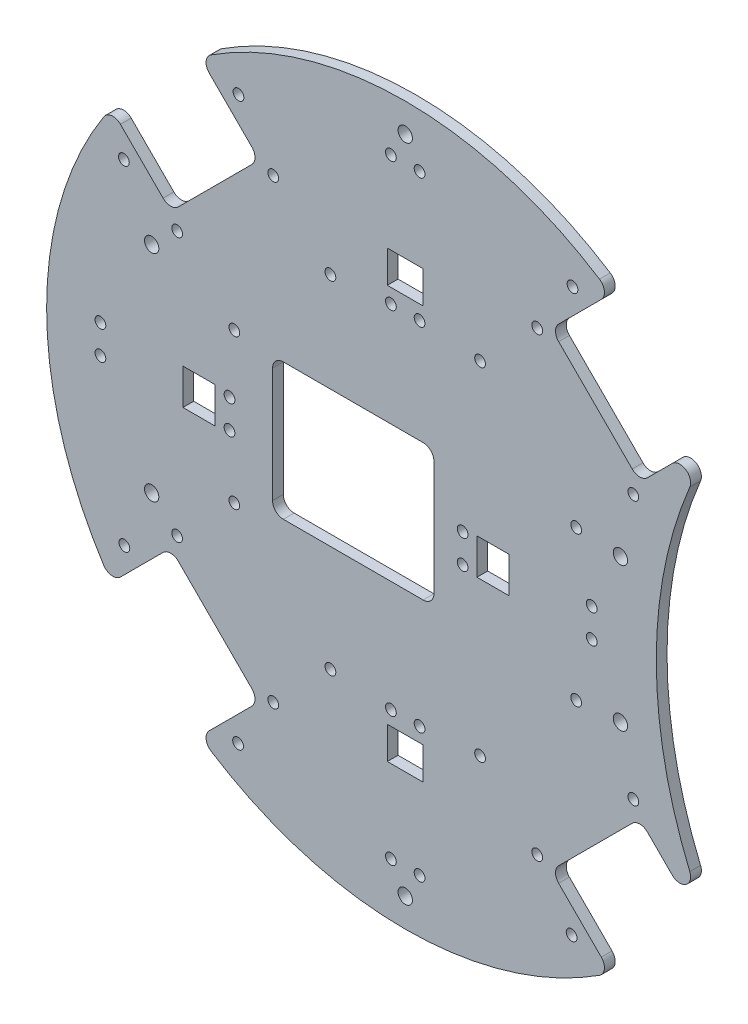
SolidWorks part; units mm, degrees
material "Caoba"
ref_plane "Alzado" through (0, 0, 0) normal (0, 0, 1) x (1, 0, 0)
ref_plane "Planta" through (0, 0, 0) normal (0, 1, 0) x (1, 0, 0)
ref_plane "Vista lateral" through (0, 0, 0) normal (1, 0, 0) x (0, 0, -1)
sketch "Croquis1" plane through (0, 0, 0) normal (0, 0, 1) x (1, 0, 0)
  circle A0 centre (0, 0) radius 100
  dimension "D1" = 200
extrude "Saliente-Extruir1" add sketch "Croquis1" along normal blind 3
sketch "Croquis3" plane through (0, 0, 3) normal (0, 0, 1) x (1, 0, 0)
  line L0 (0, 0) -> (190, 0) construction
  circle A0 centre (190, 0) radius 120
  dimension "D1" = 240
  dimension "D2" = 190
extrude "Cortar-Extruir1" cut sketch "Croquis3" against normal blind 3
sketch "Croquis5" plane through (0, 0, 3) normal (0, 0, 1) x (1, 0, 0)
  line L0 (0, -100) -> (0, 100) construction
  line L1 (-100, 0) -> (70, 0) construction
  line L2 (0, 0) -> (-70.7107, -70.7107) construction
  line L3 (-70.7107, -70.7107) -> (70.7107, 70.7107) construction
  line L4 (0, 0) -> (-70.7107, 70.7107) construction
  line L5 (-70.7107, 70.7107) -> (70.7107, -70.7107) construction
  line L6 (-70.7107, -70.7107) -> (-58.3363, -83.085) construction
  line L9 (-58.3363, -83.085) -> (-83.085, -58.3363)
  line L11 (-83.085, -58.3363) -> (-65.4074, -40.6586)
  line L12 (-65.4074, -40.6586) -> (-40.6586, -65.4074)
  line L13 (-40.6586, -65.4074) -> (-58.3363, -83.085)
  line L14 (-70.7107, 70.7107) -> (-83.085, 58.3363) construction
  line L15 (-83.085, 58.3363) -> (-100, 0) construction
  line L17 (-83.085, 58.3363) -> (-58.3363, 83.085)
  line L18 (-58.3363, 83.085) -> (-40.6586, 65.4074)
  line L19 (-40.6586, 65.4074) -> (-65.4074, 40.6586)
  line L20 (-65.4074, 40.6586) -> (-83.085, 58.3363)
  line L22 (70.7107, -70.7107) -> (58.3363, -83.085) construction
  line L23 (58.3363, -83.085) -> (0, -100) construction
  line L24 (58.3363, -83.085) -> (83.085, -58.3363)
  line L25 (83.085, -58.3363) -> (65.4074, -40.6586)
  line L26 (65.4074, -40.6586) -> (40.6586, -65.4074)
  line L27 (40.6586, -65.4074) -> (58.3363, -83.085)
  line L28 (70.7107, 70.7107) -> (58.3363, 83.085) construction
  line L29 (58.3363, 83.085) -> (0, 100) construction
  line L30 (58.3363, 83.085) -> (83.085, 58.3363)
  line L31 (83.085, 58.3363) -> (65.4074, 40.6586)
  line L32 (65.4074, 40.6586) -> (40.6586, 65.4074)
  line L33 (40.6586, 65.4074) -> (58.3363, 83.085)
  arc A0 (83.4211, 55.1446) -> (83.4211, -55.1446) centre (0, 0) ccw construction
  arc A1 (83.4211, 55.1446) -> (83.4211, -55.1446) centre (190, 0) ccw construction
  point P36 (0, 0)
  dimension "D2" = 17.5
  dimension "D3" = 25
  dimension "D4" = 35
  dimension "D5" = 25
  dimension "D6" = 35
  dimension "D8" = 25
  dimension "D9" = 17.5
  dimension "D7" = 35
  dimension "D10" = 90
  dimension "D11" = 17.5
  dimension "D12" = 17.5
  dimension "D13" = 35
  dimension "D14" = 25
  dimension "D15" = 134.3503
  dimension "D16" = 100
extrude "Cortar-Extruir6" cut sketch "Croquis5" against normal blind 10
sketch "Croquis12" plane through (0, 0, 3) normal (0, 0, 1) x (1, 0, 0)
  line L0 (-53.033, -53.033) -> (-39.9421, -50.0116) construction
  line L1 (-40.6586, -65.4074) -> (-65.4074, -40.6586) construction
  line L2 (-39.9421, -50.0116) -> (-36.8049, -63.6043) construction
  line L3 (-36.8049, -63.6043) -> (-63.6043, -36.8049) construction
  line L4 (-63.6043, -36.8049) -> (-47.6661, -20.8667) construction
  line L6 (53.033, -53.033) -> (-53.033, 53.033) construction
  line L7 (65.4074, -40.6586) -> (40.6586, -65.4074) construction
  line L8 (-65.4074, 40.6586) -> (-40.6586, 65.4074) construction
  line L9 (36.8049, 63.6043) -> (20.8667, 47.6661) construction
  line L10 (63.6043, 36.8049) -> (36.8049, 63.6043) construction
  line L11 (50.0116, 39.9421) -> (63.6043, 36.8049) construction
  line L12 (53.033, 53.033) -> (50.0116, 39.9421) construction
  line L14 (53.033, -53.033) -> (50.2046, -50.2046) construction
  line L15 (50.2046, -50.2046) -> (36.8049, -63.6043) construction
  line L16 (36.8049, -63.6043) -> (63.6043, -36.8049) construction
  line L17 (63.6043, -36.8049) -> (47.6661, -20.8667) construction
  line L19 (-53.033, -53.033) -> (53.033, 53.033) construction
  line L20 (-36.8049, 63.6043) -> (-20.8667, 47.6661) construction
  line L21 (-63.6043, 36.8049) -> (-36.8049, 63.6043) construction
  line L22 (-50.2046, 50.2046) -> (-63.6043, 36.8049) construction
  line L23 (-53.033, 53.033) -> (-50.2046, 50.2046) construction
  circle A0 centre (-63.6043, -36.8049) radius 1.5
  circle A1 centre (-36.8049, -63.6043) radius 1.5
  circle A2 centre (-47.6661, -20.8667) radius 1.5
  circle A3 centre (-20.8667, -47.6661) radius 1.5
  circle A5 centre (47.6661, 20.8667) radius 1.5
  circle A6 centre (20.8667, 47.6661) radius 1.5
  circle A7 centre (63.6043, 36.8049) radius 1.5
  circle A8 centre (36.8049, 63.6043) radius 1.5
  circle A10 centre (20.8667, -47.6661) radius 1.5
  circle A11 centre (47.6661, -20.8667) radius 1.5
  circle A12 centre (63.6043, -36.8049) radius 1.5
  circle A13 centre (36.8049, -63.6043) radius 1.5
  circle A15 centre (-63.6043, 36.8049) radius 1.5
  circle A16 centre (-36.8049, 63.6043) radius 1.5
  circle A17 centre (-20.8667, 47.6661) radius 1.5
  circle A18 centre (-47.6661, 20.8667) radius 1.5
  dimension "D2" = 3
  dimension "D3" = 3
  dimension "D4" = 4
  dimension "D5" = 4
  dimension "D6" = 3
  dimension "D7" = 3
  dimension "D8" = 37.9
  dimension "D9" = 22.54
  dimension "D10" = 22.54
  dimension "D11" = 37.9
  dimension "D12" = 18.95
  dimension "D13" = 18.95
  dimension "D14" = 3
  dimension "D15" = 3
  dimension "D16" = 3
  dimension "D17" = 3
  dimension "D18" = 37.9
  dimension "D19" = 22.54
  dimension "D20" = 22.54
  dimension "D21" = 37.9
  dimension "D22" = 4
  dimension "D1" = 13.95
extrude "Cortar-Extruir7" cut sketch "Croquis12" against normal through all
sketch "Croquis9" plane through (0, 0, 3) normal (0, 0, 1) x (1, 0, 0)
  line L0 (0, 0) -> (-100, 0) construction
  line L5 (0, 100) -> (0, -100) construction
  line L6 (20, 5) -> (29, 5)
  line L7 (20, 5) -> (20, -5)
  line L8 (20, -5) -> (29, -5)
  line L9 (29, 5) -> (29, -5)
  line L10 (-5, -53) -> (5, -53)
  line L11 (-53, 5) -> (-62, 5)
  line L12 (-53, 5) -> (-53, -5)
  line L13 (-53, -5) -> (-62, -5)
  line L14 (-62, 5) -> (-62, -5)
  line L15 (-5, 62) -> (5, 62)
  line L16 (-5, 62) -> (-5, 53)
  line L17 (-5, 53) -> (5, 53)
  line L18 (5, 62) -> (5, 53)
  line L19 (5, -62) -> (5, -53)
  line L20 (-5, -62) -> (5, -62)
  line L21 (-5, -62) -> (-5, -53)
  line L22 (0, 0) -> (70, 0) construction
  line L24 (-52.061, -4) -> (-52.0837, -4) construction
  circle A0 centre (52, -4) radius 1.5
  circle A1 centre (16, 4) radius 1.5
  circle A2 centre (20.8667, 47.6661) radius 1.5 construction
  circle A4 centre (52, 4) radius 1.5
  circle A5 centre (16, -4) radius 1.5
  arc A6 (-81.9939, 57.2451) -> (-81.9939, -57.2451) centre (0, 0) ccw construction
  arc A7 (83.4211, 55.1446) -> (83.4211, -55.1446) centre (190, 0) ccw construction
  circle A8 centre (-85, 4) radius 1.5
  circle A9 centre (-85, -4) radius 1.5
  circle A10 centre (-49, 4) radius 1.5
  circle A11 centre (-49, -4) radius 1.5
  circle A12 centre (-4, 85) radius 1.5
  circle A13 centre (4, 85) radius 1.5
  circle A14 centre (-4, 49) radius 1.5
  circle A15 centre (4, 49) radius 1.5
  circle A20 centre (-4, -49) radius 1.5
  circle A21 centre (4, -49) radius 1.5
  circle A22 centre (4, -85) radius 1.5
  circle A23 centre (-4, -85) radius 1.5
  arc A25 (57.2451, 81.9939) -> (-57.2451, 81.9939) centre (0, 0) ccw construction
  point P2 (0, 0)
  dimension "D6" = 16
  dimension "D7" = 3
  dimension "D8" = 36
  dimension "D9" = 36
  dimension "D10" = 3
  dimension "D11" = 3
  dimension "D12" = 4
  dimension "D13" = 4
  dimension "D14" = 3
  dimension "D15" = 3
  dimension "D16" = 3
  dimension "D21" = 4
  dimension "D22" = 4
  dimension "D23" = 3
  dimension "D24" = 3
  dimension "D25" = 4
  dimension "D26" = 4
  dimension "D27" = 36
  dimension "D28" = 5
  dimension "D29" = 85
  dimension "D30" = 85
  dimension "D35" = 3
  dimension "D36" = 3
  dimension "D37" = 5
  dimension "D38" = 4
  dimension "D39" = 3
  dimension "D40" = 3
  dimension "D41" = 8
  dimension "D42" = 36
  dimension "D43" = 36
  dimension "D44" = 36
  dimension "D45" = 4
  dimension "D46" = 4
  dimension "D51" = 4
  dimension "D52" = 4
  dimension "D53" = 16
  dimension "D55" = 36
  dimension "D56" = 49
  dimension "D57" = 49
  dimension "D58" = 3
  dimension "D59" = 3
  dimension "D60" = 3
  dimension "D61" = 3
  dimension "D62" = 9
  dimension "D32" = 10
  dimension "D64" = 4
  dimension "D71" = 85.0941
  dimension "D72" = 85.0941
  dimension "D19" = 4
  dimension "D31" = 36
  dimension "D49" = 4
  dimension "D50" = 5
  dimension "D65" = 4
  dimension "D68" = 16.9194
  dimension "D17" = 9
  dimension "D18" = 10
  dimension "D20" = 4
  dimension "D33" = 5
  dimension "D34" = 4
  dimension "D47" = 10
  dimension "D48" = 9
  dimension "D54" = 4
  dimension "D63" = 4
  dimension "D66" = 9
  dimension "D67" = 10
extrude "Cortar-Extruir5" cut sketch "Croquis9" against normal blind 10
sketch "Croquis13" plane through (0, 0, 3) normal (0, 0, 1) x (1, 0, 0)
  line L0 (0, 100) -> (0, -100) construction
  line L1 (-100, 0) -> (70, 0) construction
  line L2 (-70.7107, 70.7107) -> (70.7107, -70.7107) construction
  line L3 (-70.7093, -70.7093) -> (70.712, 70.712) construction
  line L4 (-70.7107, 70.7107) -> (-70.7093, -70.7093) construction
  line L5 (-70.7093, -70.7093) -> (70.7107, -70.7107) construction
  line L6 (70.7107, -70.7107) -> (70.712, 70.712) construction
  line L7 (70.712, 70.712) -> (-70.7107, 70.7107) construction
  line L9 (-37, 20) -> (8, 20)
  line L10 (-37, 20) -> (-37, -18)
  line L11 (-37, -18) -> (8, -18)
  line L12 (8, 20) -> (8, -18)
  arc A0 (57.2451, 81.9939) -> (-57.2451, 81.9939) centre (0, 0) ccw construction
  arc A1 (-57.2451, -81.9939) -> (57.2451, -81.9939) centre (0, 0) ccw construction
  arc A2 (-81.9939, 57.2451) -> (-81.9939, -57.2451) centre (0, 0) ccw construction
  arc A3 (83.4211, 55.1446) -> (83.4211, -55.1446) centre (190, 0) ccw construction
  circle A4 centre (-70.7103, 30) radius 2
  circle A5 centre (-70.7097, -30) radius 2
  circle A8 centre (0, -92) radius 2
  circle A9 centre (0, 92) radius 2
  circle A10 centre (60, -20) radius 2
  circle A11 centre (60, 20) radius 2
  point P37 (-15, 0)
  dimension "D9" = 4
  dimension "D10" = 4
  dimension "D11" = 30
  dimension "D12" = 30
  dimension "D13" = 4
  dimension "D14" = 4
  dimension "D15" = 60
  dimension "D16" = 60
  dimension "D17" = 4
  dimension "D18" = 92
  dimension "D19" = 92
  dimension "D20" = 4
  dimension "D25" = 20
  dimension "D26" = 20
  dimension "D1" = 45
  dimension "D2" = 200
  dimension "D3" = 0
  dimension "D4" = 200
  dimension "D5" = 45
  dimension "D6" = 0
  dimension "D7" = 141.42
  dimension "D8" = 141.42
  dimension "D21" = 45
  dimension "D22" = 38
  dimension "D23" = 18
  dimension "D24" = 37
extrude "Cortar-Extruir8" cut sketch "Croquis13" against normal through all
fillet "Redondeo2" radius 3 20 edges at (-81.9939, 57.2451, 1.5) (-65.4074, 40.6586, 1.5) (-40.6586, 65.4074, 1.5) (-57.2451, 81.9939, 1.5) (65.4074, 40.6586, 1.5) (40.6586, 65.4074, 1.5) (57.2451, 81.9939, 1.5) (81.9939, 57.2451, 1.5) (65.4074, -40.6586, 1.5) (40.6586, -65.4074, 1.5) (81.9939, -57.2451, 1.5) (57.2451, -81.9939, 1.5) (-65.4074, -40.6586, 1.5) (-81.9939, -57.2451, 1.5) (-57.2451, -81.9939, 1.5) (-40.6586, -65.4074, 1.5) (8, -18, 1.5) (8, 20, 1.5) (-37, -18, 1.5) (-37, 20, 1.5)
fillet "Redondeo3" radius 3 2 edges at (83.4211, -55.1446, 1.5) (83.4211, 55.1446, 1.5)
sketch "Croquis14" plane through (0, 0, 3) normal (0, 0, 1) x (1, 0, 0)
  line L0 (42.78, -67.5287) -> (54.6657, -79.4145) construction
  line L1 (-54.6657, -79.4145) -> (-42.78, -67.5287) construction
  line L3 (-67.5287, -42.78) -> (-79.4145, -54.6657) construction
  line L4 (-79.4145, 54.6657) -> (-67.5287, 42.78) construction
  line L5 (-42.78, 67.5287) -> (-54.6657, 79.4145) construction
  line L6 (54.6657, 79.4145) -> (42.78, 67.5287) construction
  circle A0 centre (46.3901, -78.2099) radius 1.5
  circle A1 centre (36.8049, -63.6043) radius 1.5 construction
  circle A2 centre (-46.6139, -78.4337) radius 1.5
  circle A3 centre (-36.8049, -63.6043) radius 1.5 construction
  circle A4 centre (-78.3182, -46.4984) radius 1.5
  circle A5 centre (-78.4553, 46.6355) radius 1.5
  circle A6 centre (-46.4984, 78.3182) radius 1.5
  circle A7 centre (46.6355, 78.4553) radius 1.5
  circle A8 centre (-63.6043, -36.8049) radius 1.5 construction
  circle A9 centre (-63.6043, 36.8049) radius 1.5 construction
  circle A10 centre (36.8049, 63.6043) radius 1.5 construction
  circle A11 centre (-36.8049, 63.6043) radius 1.5 construction
  dimension "D1" = 3
  dimension "D2" = 5
  dimension "D3" = 17.47
  dimension "D4" = 3
  dimension "D5" = 17.78
  dimension "D7" = 3
  dimension "D8" = 3
  dimension "D9" = 3
  dimension "D10" = 3
  dimension "D11" = 5
  dimension "D12" = 17.62
  dimension "D13" = 17.81
  dimension "D14" = 5
  dimension "D15" = 5
  dimension "D16" = 5
  dimension "D17" = 17.81
  dimension "D18" = 17.62
  dimension "D6" = 5
extrude "Cortar-Extruir9" cut sketch "Croquis14" against normal through all
